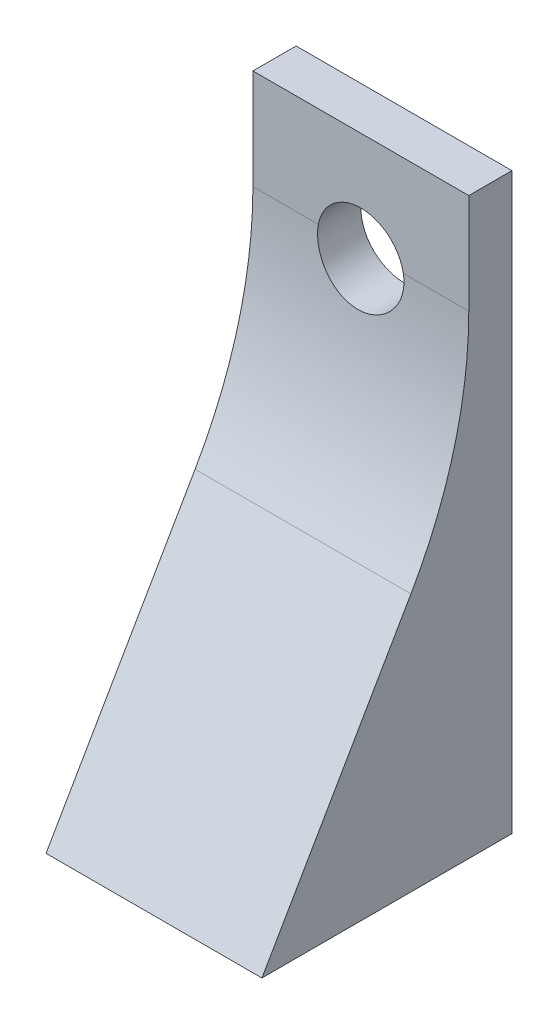
SolidWorks part; units mm, degrees
ref_plane "前视基准面" through (0, 0, 0) normal (0, 0, 1) x (1, 0, 0)
ref_plane "上视基准面" through (0, 0, 0) normal (0, 1, 0) x (1, 0, 0)
ref_plane "右视基准面" through (0, 0, 0) normal (1, 0, 0) x (0, 0, -1)
sketch "草图1" plane through (0, 0, 0) normal (0, 0, 1) x (1, 0, 0)
  line L1 (-2.5, 6.65) -> (2.5, 6.65)
  line L2 (-2.5, 6.65) -> (-2.5, -6.65)
  line L3 (-2.5, -6.65) -> (2.5, -6.65)
  line L4 (2.5, 6.65) -> (2.5, -6.65)
  line L5 (-2.5, 6.65) -> (2.5, -6.65) construction
  line L6 (-2.5, -6.65) -> (2.5, 6.65) construction
  circle A0 centre (0, 4.15) radius 1
  point P0 (0, 0)
  point P9 (0, 6.65)
  dimension "D3" = 2
  dimension "D1" = 13.3
  dimension "D2" = 5
  dimension "D4" = 2.5
extrude "凸台-拉伸1" add sketch "草图1" along normal blind 1
sketch "草图2" plane through (0, 0, 0) normal (1, 0, 0) x (0, 0, -1)
  line L0 (-1, 1.65) -> (-5.792, -6.65)
  line L1 (-1, -6.65) -> (-1, 6.65) construction
  line L2 (-5.792, -6.65) -> (-1, -6.65)
  line L3 (-1, -6.65) -> (-1, 1.65)
  line L4 (-1, 6.65) -> (0, 6.65) construction
  dimension "D1" = 5
  dimension "D2" = 60
extrude "凸台-拉伸3" add sketch "草图2" along normal mid plane 5
fillet "圆角1" radius 10 1 edges at (0, 1.65, 1)
